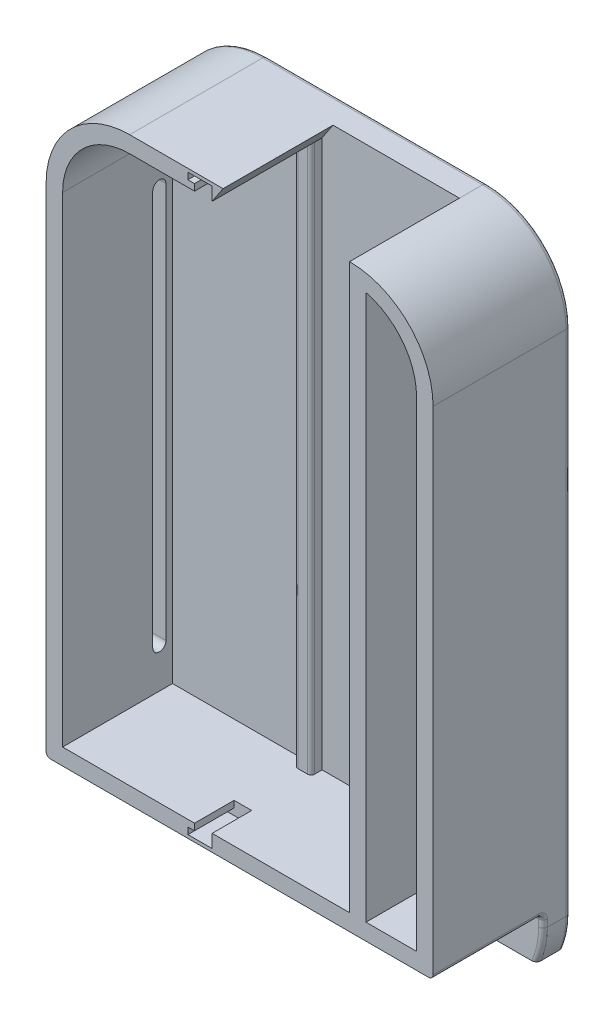
SolidWorks part; units mm, degrees
ref_plane "정면" through (0, 0, 0) normal (0, 0, 1) x (1, 0, 0)
ref_plane "윗면" through (0, 0, 0) normal (0, 1, 0) x (1, 0, 0)
ref_plane "우측면" through (0, 0, 0) normal (1, 0, 0) x (0, 0, -1)
sketch "스케치1" plane through (0, 0, 0) normal (0, 0, 1) x (1, 0, 0)
  line L0 (-54.9658, -124.1091) -> (-84.9652, -124.1091)
  line L1 (55.0342, -124.1091) -> (85.0335, -124.1091)
  line L12 (50.0342, 159.841) -> (-49.9658, 159.841)
  line L13 (-87.9658, 121.841) -> (-87.9658, -109.309)
  line L15 (-44.9671, -114.109) -> (45.0354, -114.109)
  line L17 (88.0342, -109.309) -> (88.0342, 121.841)
  arc A8 (-49.9658, 159.841) -> (-87.9658, 121.841) centre (-49.9658, 121.841) ccw
  arc A9 (-87.9658, -109.309) -> (-84.9652, -124.1091) centre (-49.9658, -109.309) ccw
  arc A10 (85.0335, -124.1091) -> (88.0342, -109.309) centre (50.0342, -109.309) ccw
  arc A11 (88.0342, 121.841) -> (50.0342, 159.841) centre (50.0342, 121.841) ccw
  ellipse E4 centre (-44.9655, -124.1105) end of major axis (-49.4382, -115.1644) minor radius 10 (-44.9671, -114.109) -> (-54.9658, -124.1091) ccw
  ellipse E5 centre (45.0338, -124.1105) end of major axis (40.5611, -133.0566) minor radius 10 (55.0342, -124.1091) -> (45.0354, -114.109) ccw
extrude "보스-돌출1" add sketch "스케치1" along normal blind 5
sketch "스케치2" plane through (0, 0, 5) normal (0, 0, 1) x (1, 0, 0)
  line L1 (-87.9658, 121.841) -> (-87.9658, -109.309) construction
  line L2 (-44.9671, -114.109) -> (45.0354, -114.109) construction
  line L3 (-87.9658, -104.109) -> (-80.4658, -104.109)
  line L4 (88.0342, 121.841) -> (88.0342, -104.109)
  line L5 (88.0342, -109.309) -> (88.0342, 121.841) construction
  line L6 (80.5342, -104.109) -> (88.0342, -104.109)
  line L8 (80.5342, 121.841) -> (80.5342, -96.609)
  line L9 (50.0342, 152.341) -> (-49.9658, 152.341)
  line L10 (-80.4658, 121.841) -> (-80.4658, -96.609)
  line L11 (-80.4658, -96.609) -> (80.5342, -96.609)
  line L18 (50.0342, 159.841) -> (-49.9658, 159.841)
  line L19 (-87.9658, 121.841) -> (-87.9658, -109.309)
  line L20 (-84.9652, -124.1091) -> (-54.9658, -124.1091)
  line L21 (-44.967, -114.109) -> (45.0353, -114.109)
  line L22 (-84.9652, -124.1091) -> (-54.9658, -124.1091)
  line L23 (88.0342, -109.309) -> (88.0342, 121.841)
  line L24 (50.0342, 159.841) -> (-49.9658, 159.841)
  line L30 (-80.4658, 121.841) -> (-80.4658, -104.109) construction
  line L31 (-80.4658, -104.109) -> (80.5342, -104.109)
  line L35 (80.5342, 121.841) -> (80.5342, -104.109) construction
  line L39 (-87.9658, 121.841) -> (-87.9658, -104.109) construction
  line L43 (55.0342, -124.1091) -> (85.0335, -124.1091)
  line L44 (55.0342, -124.1091) -> (85.0335, -124.1091)
  arc A0 (80.5342, 121.841) -> (50.0342, 152.341) centre (50.0342, 121.841) ccw
  arc A1 (-49.9658, 152.341) -> (-80.4658, 121.841) centre (-49.9658, 121.841) ccw
  circle A3 centre (-74.1658, -79.5024) radius 4.5
  circle A4 centre (74.2342, -79.5024) radius 4.5
  circle A5 centre (-71.379, -47.709) radius 4.5
  circle A6 centre (-74.1658, -79.5024) radius 5.5
  circle A7 centre (71.021, -47.709) radius 4.5
  arc A12 (88.0342, 121.841) -> (50.0342, 159.841) centre (50.0342, 121.841) ccw
  arc A13 (-49.9658, 159.841) -> (-87.9658, 121.841) centre (-49.9658, 121.841) ccw
  arc A14 (-87.9658, -109.309) -> (-84.9652, -124.1091) centre (-49.9658, -109.309) ccw
  arc A15 (85.0335, -124.1091) -> (88.0342, -109.309) centre (50.0342, -109.309) ccw
  arc A16 (88.0342, 121.841) -> (50.0342, 159.841) centre (50.0342, 121.841) ccw
  arc A17 (-49.9658, 159.841) -> (-87.9658, 121.841) centre (-49.9658, 121.841) ccw
  circle A20 centre (73.9443, 9.6991) radius 2.4
  circle A21 centre (73.9443, -10.2515) radius 3
  circle A22 centre (-73.8759, 9.6991) radius 2.4
  circle A23 centre (-73.8759, -10.2515) radius 3
  circle A24 centre (-73.8759, 89.6991) radius 2.4
  circle A25 centre (73.9443, 89.6991) radius 2.4
  circle A26 centre (73.9443, 109.7485) radius 2.9541
  circle A27 centre (-73.8759, 109.7485) radius 3
  circle A28 centre (-14.9658, 146.841) radius 1.8
  circle A29 centre (15.0342, 146.841) radius 1.8
  ellipse E6 centre (-44.9655, -124.1105) end of major axis (-49.4382, -115.1644) minor radius 10 (-44.967, -114.109) -> (-54.9658, -124.1091) ccw
  ellipse E7 centre (45.0338, -124.1105) end of major axis (40.5611, -133.0566) minor radius 10 (55.0342, -124.1091) -> (45.0353, -114.109) ccw
  arc M13 (88.0342, 121.841) -> (50.0342, 159.841) centre (50.0342, 121.841) ccw
  line M14 (50.0342, 159.841) -> (-49.9658, 159.841)
  arc M15 (-49.9658, 159.841) -> (-87.9658, 121.841) centre (-49.9658, 121.841) ccw
  line M16 (-87.9658, 121.841) -> (-87.9658, -109.309)
  line M24 (88.0342, -109.309) -> (88.0342, 121.841)
  dimension "D4" = 10
  dimension "D1" = 0
  dimension "D2" = 7.5
extrude "보스-돌출2" add sketch "스케치2" along normal blind 50 contours L3 L31 L6 A1 L9 A0 L8 L11 L10 M24 M13 M14 M15 M16 region at (-84.7934, 8.866, 5)
sketch "스케치7" plane through (0, 152.341, 0) normal (0, -1, 0) x (1, 0, 0)
  line L0 (50.0342, 5) -> (-49.9658, 5) construction
  line L1 (50.0342, 5) -> (-7.4658, 5)
  line L2 (50.0342, 5) -> (50.0342, 55)
  line L3 (50.0342, 55) -> (-7.4658, 55)
  line L4 (-7.4658, 5) -> (-7.4658, 55)
  line L5 (50.0342, 5) -> (-49.9658, 5) construction
  line L6 (50.0342, 55) -> (-49.9658, 55) construction
  line L7 (50.0342, 55) -> (50.0342, 5) construction
  dimension "D1" = 57.5
extrude "컷-돌출1" cut sketch "스케치7" against normal up to next
ref_plane "평면2" through (0, 142.341, 0) normal (0, -1, 0) x (-1, 0, 0)
sketch "스케치13" plane through (0, 142.341, 0) normal (0, -1, 0) x (-1, 0, 0)
  line L1 (-50.0342, -55) -> (-57.5342, -55)
  line L2 (-50.0342, -55) -> (-50.0342, -5)
  line L3 (-50.0342, -5) -> (-57.5342, -5)
  line L4 (-57.5342, -55) -> (-57.5342, -5)
  line L5 (-50.0342, -55) -> (-50.0342, -5) construction
  dimension "D1" = 7.5
extrude "보스-돌출5" add sketch "스케치13" along normal up to next and the other way up to next
sketch "스케치15" plane through (0, 0, 55) normal (0, 0, 1) x (1, 0, 0)
  line L0 (-7.4658, 152.341) -> (-49.9658, 152.341) construction
  line L4 (-20.4658, 152.341) -> (-20.4658, 155.341)
  line L5 (-80.4658, -96.609) -> (50.0342, -96.609) construction
  line L10 (-7.4658, 159.841) -> (-7.4658, 152.341) construction
  line L11 (-23.4658, 158.341) -> (-12.4658, 158.341)
  line L14 (-20.4658, 155.341) -> (-23.4658, 155.341)
  line L15 (-23.4658, 158.341) -> (-23.4658, 155.341)
  line L19 (-12.4658, 158.341) -> (-12.4658, 155.341)
  line L22 (-23.4658, -102.609) -> (-23.4658, -99.609)
  line L23 (-20.4658, -99.609) -> (-23.4658, -99.609)
  line L24 (-12.4658, -102.609) -> (-23.4658, -102.609)
  line L25 (-20.4658, -96.609) -> (-20.4658, -99.609)
  line L27 (-12.4658, -102.609) -> (-12.4658, -99.609)
  line L28 (-12.4658, 155.341) -> (-12.4658, 152.341)
  line L29 (-12.4658, 152.341) -> (-20.4658, 152.341)
  line L30 (-12.4658, -99.609) -> (-12.4658, -96.609)
  line L31 (-12.4658, -96.609) -> (-20.4658, -96.609)
  dimension "D1" = 11
  dimension "D2" = 3
  dimension "D3" = 11
  dimension "D4" = 16
  dimension "D5" = 3
  dimension "D6" = 3
  dimension "D7" = 6
  dimension "D9" = 3
  dimension "D11" = 3
extrude "컷-돌출2" cut sketch "스케치15" against normal blind 18
sketch "스케치17" plane through (0, 0, 5) normal (0, 0, 1) x (1, 0, 0)
  line L0 (-80.4658, -96.609) -> (50.0342, -96.609) construction
  line L1 (-12.4658, 152.341) -> (-19.9658, 152.341)
  line L2 (-12.4658, 152.341) -> (-12.4658, -96.609)
  line L3 (-12.4658, -96.609) -> (-19.9658, -96.609)
  line L4 (-19.9658, 152.341) -> (-19.9658, -96.609)
  line L5 (-7.4658, 152.341) -> (-49.9658, 152.341) construction
  line L6 (50.0342, 159.841) -> (50.0342, -96.609) construction
  dimension "D1" = 7.5
  dimension "D2" = 62.5
extrude "보스-돌출6" add sketch "스케치17" along normal blind 5
sketch "스케치22" plane through (-80.4658, 0, 0) normal (1, 0, 0) x (0, 0, -1)
  line L0 (-11, 101.841) -> (-11, -78.159) construction
  line L1 (-8, 101.841) -> (-8, -78.159)
  line L2 (-14, 101.841) -> (-14, -78.159)
  line L3 (0, 121.841) -> (0, -109.309) construction
  line L4 (-55, 121.841) -> (0, 121.841) construction
  arc A0 (-8, 101.841) -> (-14, 101.841) centre (-11, 101.841) ccw
  arc A1 (-14, -78.159) -> (-8, -78.159) centre (-11, -78.159) ccw
  point P2 (-11, 11.841)
  dimension "D1" = 6
  dimension "D2" = 8
  dimension "D3" = 180
  dimension "D4" = 20
extrude "컷-돌출3" cut sketch "스케치22" against normal through all
sketch "스케치24" plane through (0, 0, 0) normal (0, 0, -1) x (-1, 0, 0)
  line L6 (-85.0335, -124.1091) -> (-55.0342, -124.1091)
  line L7 (-85.0335, -124.1091) -> (-55.0342, -124.1091)
  line L8 (54.9658, -124.1091) -> (84.9652, -124.1091)
  line L9 (54.9658, -124.1091) -> (84.9652, -124.1091)
  line L18 (-88.0342, 121.841) -> (-88.0342, -109.309)
  line L20 (-45.0354, -114.109) -> (44.9671, -114.109)
  line L22 (87.9658, -109.309) -> (87.9658, 121.841)
  line L23 (49.9658, 159.841) -> (-50.0342, 159.841)
  line L24 (-88.0342, 121.841) -> (-88.0342, -109.309)
  line L26 (-45.0354, -114.109) -> (44.9671, -114.109)
  line L28 (87.9658, -109.309) -> (87.9658, 121.841)
  line L29 (49.9658, 159.841) -> (-50.0342, 159.841)
  arc A12 (-50.0342, 159.841) -> (-88.0342, 121.841) centre (-50.0342, 121.841) ccw
  arc A13 (-88.0342, -109.309) -> (-85.0335, -124.1091) centre (-50.0342, -109.309) ccw
  arc A14 (84.9652, -124.1091) -> (87.9658, -109.309) centre (49.9658, -109.309) ccw
  arc A15 (87.9658, 121.841) -> (49.9658, 159.841) centre (49.9658, 121.841) ccw
  arc A16 (-50.0342, 159.841) -> (-88.0342, 121.841) centre (-50.0342, 121.841) ccw
  arc A17 (-88.0342, -109.309) -> (-85.0335, -124.1091) centre (-50.0342, -109.309) ccw
  arc A18 (84.9652, -124.1091) -> (87.9658, -109.309) centre (49.9658, -109.309) ccw
  arc A19 (87.9658, 121.841) -> (49.9658, 159.841) centre (49.9658, 121.841) ccw
  ellipse E6 centre (-45.0338, -124.1105) end of major axis (-49.5065, -115.1644) minor radius 10 (-45.0354, -114.109) -> (-55.0342, -124.1091) ccw
  ellipse E7 centre (44.9655, -124.1105) end of major axis (49.4382, -115.1644) minor radius 10 (54.9658, -124.1091) -> (44.9671, -114.109) ccw
  ellipse E8 centre (-45.0338, -124.1105) end of major axis (-49.5065, -115.1644) minor radius 10 (-45.0354, -114.109) -> (-55.0342, -124.1091) ccw
  ellipse E9 centre (44.9655, -124.1105) end of major axis (49.4382, -115.1644) minor radius 10 (54.9658, -124.1091) -> (44.9671, -114.109) ccw
  dimension "D1" = 0
extrude "보스-돌출7" add sketch "스케치24" along normal blind 7.5
sketch "스케치25" plane through (0, 0, -7.5) normal (0, 0, -1) x (-1, 0, 0)
  circle A0 centre (-71.021, -47.709) radius 10.5
  circle A1 centre (71.379, -47.709) radius 10.5
  circle A2 centre (74.1658, -79.5024) radius 10.5
  circle A3 centre (-74.2342, -79.5024) radius 10.5
  dimension "D1" = 21
extrude "컷-돌출4" cut sketch "스케치25" against normal blind 7
sketch "스케치27" plane through (0, 0, -7.5) normal (0, 0, -1) x (-1, 0, 0)
  line L10 (-40.0342, 143.341) -> (39.9658, 143.341) construction
  line L11 (-40.0342, 150.841) -> (39.9658, 150.841)
  line L12 (-40.0342, 135.841) -> (39.9658, 135.841)
  line L13 (49.9658, 159.841) -> (-50.0342, 159.841) construction
  line L14 (-88.0342, 121.841) -> (-88.0342, -109.309) construction
  line L15 (87.9658, -109.309) -> (87.9658, 121.841) construction
  arc A2 (-40.0342, 150.841) -> (-40.0342, 135.841) centre (-40.0342, 143.341) ccw
  arc A3 (39.9658, 135.841) -> (39.9658, 150.841) centre (39.9658, 143.341) ccw
  point P8 (-0.0342, 143.341)
  dimension "D2" = 48
  dimension "D7" = 7.5
  dimension "D3" = 48
  dimension "D1" = 9
extrude "컷-돌출5" cut sketch "스케치27" against normal blind 7
sketch "스케치29" plane through (0, 0, 55) normal (0, 0, 1) x (1, 0, 0)
  line L0 (-7.4658, 159.841) -> (-12.4658, 152.341)
  line L1 (-7.4658, 152.341) -> (-12.4658, 152.341) construction
  line L2 (-12.4658, 152.341) -> (-7.4658, 152.341)
  line L3 (-7.4658, 152.341) -> (-7.4658, 159.841)
  line L5 (-12.4658, -96.609) -> (-12.4658, 152.341) construction
  line L6 (-12.4658, 152.341) -> (-19.9658, 152.341) construction
extrude "컷-돌출6" cut sketch "스케치29" against normal blind 50
fillet "필렛1" radius 2 19 edges at (-87.2081, -116.8596, 5) (87.2765, -116.8596, 5) (-87.9658, -106.709, 5) (88.0342, -106.709, 5) (0.0342, -104.109, 5) (88.0342, -104.109, 30) (-87.9658, -104.109, 30) (52.1057, -117.0379, -7.5) (0.0342, -114.109, -7.5) (-87.2081, -116.8596, -7.5) (-87.9658, 6.266, -7.5) (-76.8359, 148.7111, -7.5) (0.0342, 159.841, -7.5) (76.9042, 148.7111, -7.5) (87.2765, -116.8596, -7.5) (-52.0374, -117.0379, -7.5) (-69.9655, -124.1091, -7.5) (70.0339, -124.1091, -7.5) (88.0342, 6.266, -7.5)
fillet "필렛2" radius 1.5 2 edges at (-19.9658, 27.866, 10) (-12.4658, 27.866, 10)
